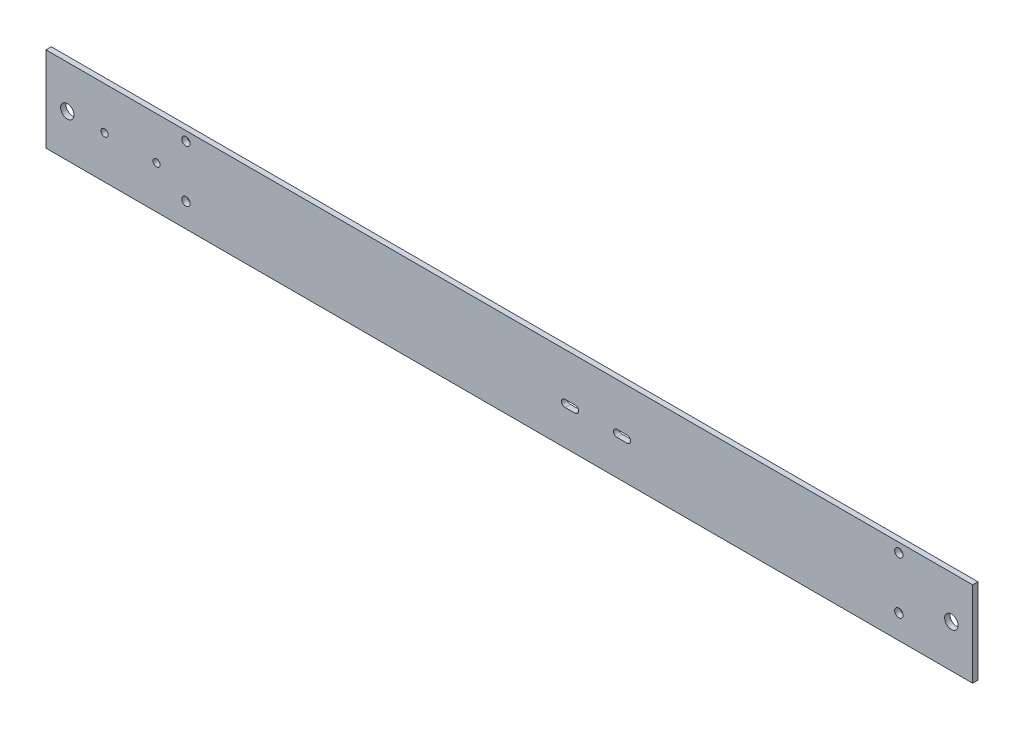
SolidWorks part; units mm, degrees
ref_plane "Front Plane" through (0, 0, 0) normal (0, 0, 1) x (1, 0, 0)
ref_plane "Top Plane" through (0, 0, 0) normal (0, 1, 0) x (1, 0, 0)
ref_plane "Right Plane" through (0, 0, 0) normal (1, 0, 0) x (0, 0, -1)
sketch "Sketch1" plane through (0, 0, 0) normal (1, 0, 0) x (0, 0, -1)
  line L0 (0, 0) -> (-3.175, 0)
  line L3 (-3.175, 0) -> (-3.175, 50.8)
  line L4 (-3.175, 50.8) -> (0, 50.8)
  line L5 (0, 50.8) -> (0, 0)
  dimension "LHeight" = 50.8
  dimension "LMaterialThickness" = 3.175
extrude "Boss-Extrude1" add sketch "Sketch1" along normal blind 552.45
sketch "SideHoles-Sketch4" plane through (0, 0, 3.175) normal (0, 0, 1) x (1, 0, 0)
  line L0 (552.45, 50.8) -> (0, 50.8) construction
  line L4 (552.45, 0) -> (0, 0) construction
  line L6 (0, 50.8) -> (0, 0) construction
  line L7 (552.45, 50.8) -> (552.45, 0) construction
  line L10 (309.425, 23) -> (315.425, 23) construction
  line L11 (309.425, 25.1) -> (315.425, 25.1)
  line L12 (309.425, 20.9) -> (315.425, 20.9)
  line L13 (340.425, 23) -> (346.425, 23) construction
  line L14 (340.425, 25.1) -> (346.425, 25.1)
  line L15 (340.425, 20.9) -> (346.425, 20.9)
  line L20 (552.45, 0) -> (552.45, 50.8) construction
  circle A6 centre (12.7, 25.4) radius 4
  circle A9 centre (539.75, 25.4) radius 4
  circle A11 centre (83.425, 45.3) radius 2.5
  arc A41 (309.425, 25.1) -> (309.425, 20.9) centre (309.425, 23) ccw
  arc A42 (315.425, 20.9) -> (315.425, 25.1) centre (315.425, 23) ccw
  arc A43 (340.425, 25.1) -> (340.425, 20.9) centre (340.425, 23) ccw
  arc A44 (346.425, 20.9) -> (346.425, 25.1) centre (346.425, 23) ccw
  circle A45 centre (83.425, 14.3) radius 2.5
  circle A46 centre (508.425, 45.3) radius 2.5
  circle A47 centre (508.425, 14.3) radius 2.5
  circle A52 centre (34.9, 25.4) radius 2.1
  circle A53 centre (65.9, 25.4) radius 2.1
  point P19 (312.425, 23)
  point P66 (343.425, 23)
  dimension "D3" = 8
  dimension "D10" = 5
  dimension "D13" = 4.2
  dimension "D2" = 12.7
  dimension "D4" = 12.7
  dimension "D6" = 31
  dimension "D14" = 209.025
  dimension "D8" = 31
  dimension "D9" = 5.5
  dimension "D11" = 44.025
  dimension "D12" = 425
  dimension "D5" = 6
  dimension "D15" = 27.8
  dimension "D20" = 240.025
  dimension "D21" = 469.025
  dimension "D24" = 539.75
  dimension "D7" = 25.4
  dimension "D16" = 36.5
  dimension "D17" = 34.9
  dimension "D18" = 31
  dimension "D19" = 486.55
  dimension "D22" = 517.55
extrude "SideHoles-Cut-Extrude3" cut sketch "SideHoles-Sketch4" against normal through all
equation "\"MidLeftOrRightSideRailHeight\"= 2.0in"
equation "\"RailThickness\"= .125in'Spec"
equation "\"VSWidth\"= 1.25in'Spec"
equation "\"LHeight@Sketch1\"=\"MidLeftOrRightSideRailHeight\""
equation "\"LMaterialThickness@Sketch1\"=\"RailThickness\""
equation "\"D1@Boss-Extrude1\" = \"SideRailLength\""
equation "\"SideRailLength\"= 21.75in"
equation "\"DistanceFromFrontSideToBedFrontYSValue\"= 48.525mm"
equation "\"DistanceBetweenFrontToBackStepperHoles\"= \"BedLength\" - \"BuildPlateStandoffHolesDistanceFromFrontOrBackSide\" * 2'Equals 270"
equation "\"BedLength\"= \"BuildPlateLength\""
equation "\"DistanceFromFrontSideToFirstLeftStepperHoleMountYSValue\"= 74.025mm"
equation "\"FrameFastenerHoleOffsetFromEdge\"= \"VSWidth\" / 2 - \"GapBetweenVerticalSupportsAndRails\" / 2"
equation "\"D2@SideHoles-Sketch4\"=\"FrameFastenerHoleOffsetFromEdge\""
equation "\"FrameFastenerHoleDiameter\"= 8mm"
equation "\"D3@SideHoles-Sketch4\"=\"FrameFastenerHoleDiameter\""
equation "\"D4@SideHoles-Sketch4\"=\"FrameFastenerHoleOffsetFromEdge\""
equation "\"StepperMountSlotDiameterOnRails\"= 4.2mm"
equation "\"StepperMountSlotWidth\"= 6mm"
equation "\"D6@SideHoles-Sketch4\" = \"Nema17StepperMountSlotDistance\""
equation "\"D14@SideHoles-Sketch4\" = \"DistanceFromFrontSideToMidRightStepperHoleMount\""
equation "\"D9@SideHoles-Sketch4\"=\"SK8MountHoleFromEitherEnd\""
equation "\"D11@SideHoles-Sketch4\"=\"DistanceFromFrontSideToBedFrontYSValue\" - ( \"SK8RodShaftSupportLength\" / 2 ) + 3mm"
equation "\"SK8RodShaftSupportLength\"= 15mm"
equation "\"D8@SideHoles-Sketch4\" = \"Nema17StepperMountSlotDistance\""
equation "\"D12@SideHoles-Sketch4\"=\"RodShaft440mmLength\" - \"SK8RodShaftSupportLength\""
equation "\"RodShaft440mmLength\"= 440mm"
equation "\"BuildPlateStandoffHolesDistanceFromFrontOrBackSide\"= 41mm"
equation "\"Nema17StepperMountSlotDistance\"= 31mm'Spec"
equation "\"DistanceFromFrontSideToMidRightStepperHoleMount\"= \"DistanceFromFrontSideToFirstLeftStepperHoleMountYSValue\" + \"DistanceBetweenFrontToBackStepperHoles\" / 2'Equals 209.025"
equation "\"D5@SideHoles-Sketch4\"=\"StepperMountSlotWidth\""
equation "\"D13@SideHoles-Sketch4\"=\"StepperMountSlotDiameterOnRails\""
equation "\"SK8MountHoleFromEitherEnd\"= 5.5mm"
equation "\"BuildPlateLength\"= 352mm'Spec"
equation "\"GapBetweenVerticalSupportsAndRails\"= \"RailThickness\" * 2"
equation "\"D15@SideHoles-Sketch4\"=27.8"
equation "\"D7@SideHoles-Sketch4\"=\"MidLeftOrRightSideRailHeight\"/2"
equation "\"DistanceFromBackToFirstGantryStepperHole\"= \"VSWidth\" - \"RailThickness\" + ( \"Nema17MountWidth\" - \"Nema17StepperMountSlotDistance\" ) / 2 - \"GapBetweenVerticalSupportsAndRails\" / 2'Equals 34.9. Push Gantry stepper as far back as possible"
equation "\"D17@SideHoles-Sketch4\"=\"DistanceFromBackToFirstGantryStepperHole\""
equation "\"D18@SideHoles-Sketch4\" = \"Nema17StepperMountSlotDistance\""
equation "\"Nema17MountWidth\"= 50mm'Spec"
